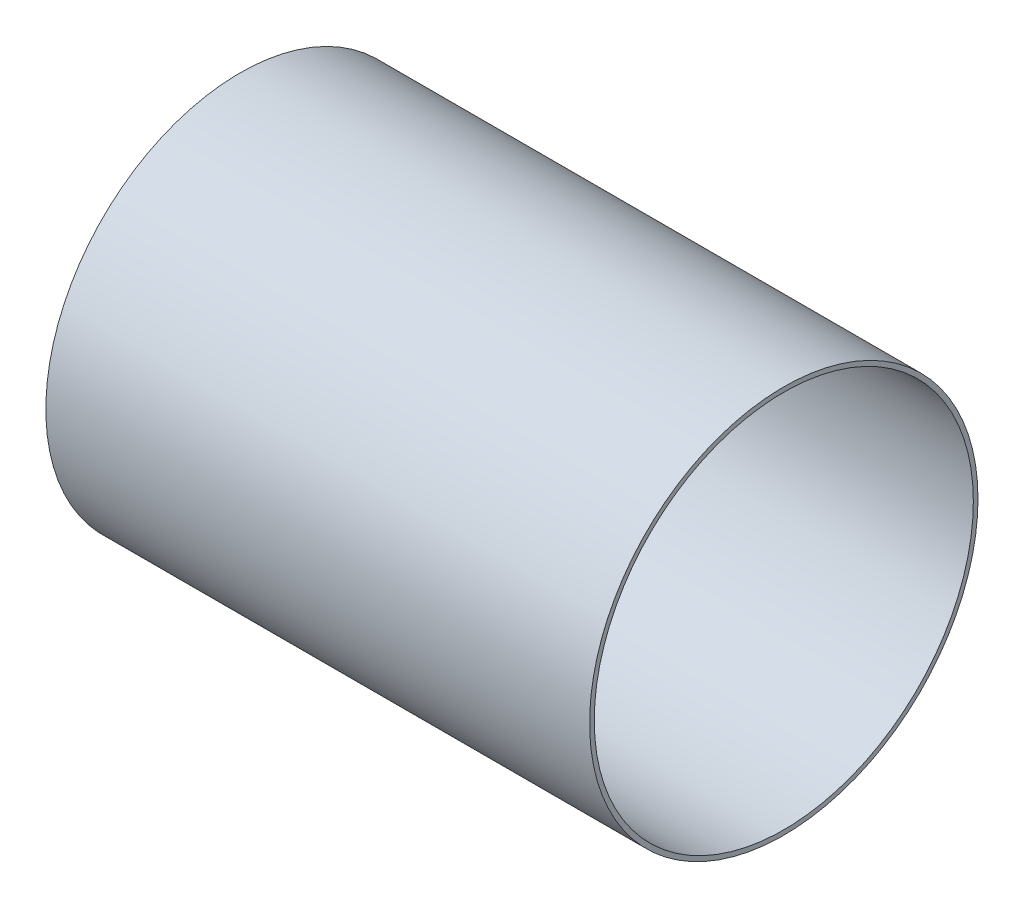
SolidWorks part; units mm, degrees
material "1060-H12"
ref_plane "Front Plane" through (0, 0, 0) normal (0, 0, 1) x (1, 0, 0)
ref_plane "Top Plane" through (0, 0, 0) normal (0, 1, 0) x (1, 0, 0)
ref_plane "Right Plane" through (0, 0, 0) normal (1, 0, 0) x (0, 0, -1)
sketch "Sketch1" plane through (0, 0, 0) normal (1, 0, 0) x (0, 0, -1)
  circle A0 centre (0, 0) radius 125
  circle A1 centre (0, 0) radius 122
  dimension "D1" = 250
  dimension "D2" = 3
extrude "Boss-Extrude1" add sketch "Sketch1" along normal blind 350
sketch "Sketch2" plane through (0, 0, 0) normal (1, 0, 0) x (0, 0, -1)
  circle A0 centre (0, 0) radius 200
ref_plane "Plane1" through (-180, 0, 0) normal (1, 0, 0) x (0, 0, -1)
